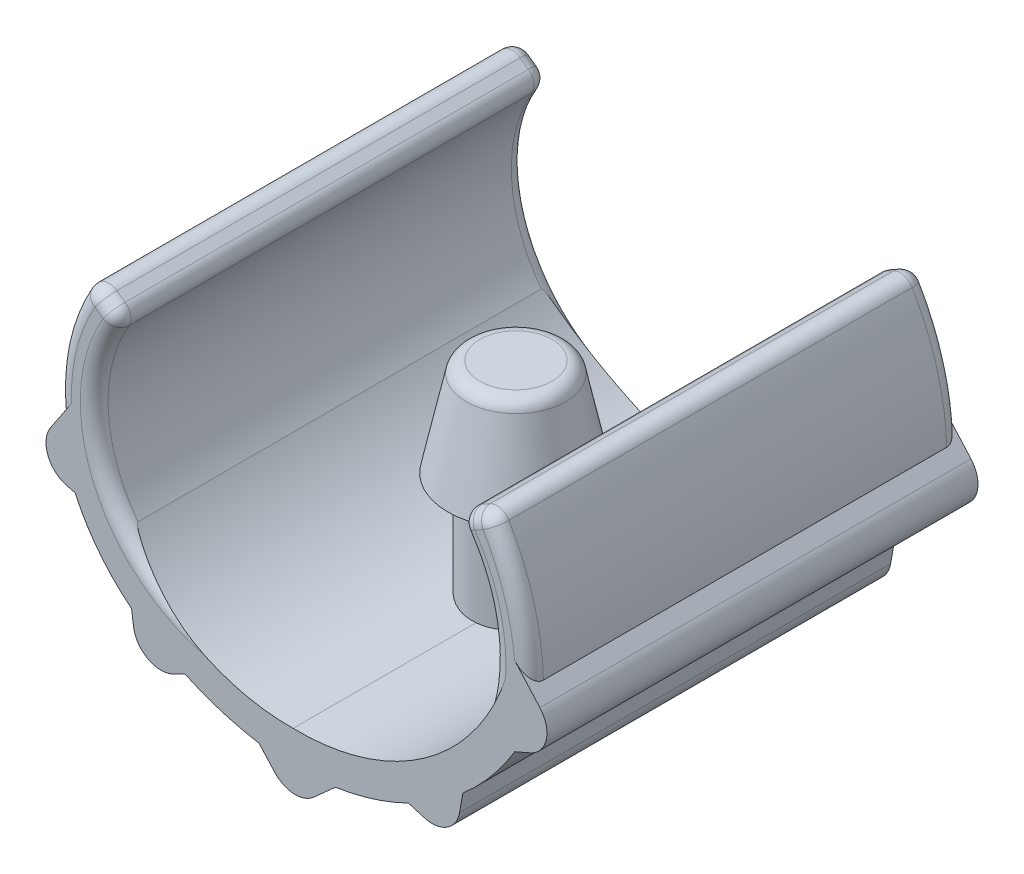
SolidWorks part; units mm, degrees
ref_plane "Front Plane" through (0, 0, 0) normal (0, 0, 1) x (1, 0, 0)
ref_plane "Top Plane" through (0, 0, 0) normal (0, 1, 0) x (1, 0, 0)
ref_plane "Right Plane" through (0, 0, 0) normal (1, 0, 0) x (0, 0, -1)
sketch "Sketch1" plane through (0, 0, 0) normal (0, 0, 1) x (1, 0, 0)
  line L0 (-248.758, 1.0447) -> (261.9086, 1.0447) construction
  line L1 (-173.9494, 133.0489) -> (-205.5576, 155.7204)
  line L2 (163.6266, 136.7807) -> (197.8189, 155.7204)
  line L3 (-237.9986, 19.6907) -> (-268.7856, -26.37)
  line L4 (-268.7856, -26.37) -> (-221.5833, -38.0173)
  line L5 (-164.251, -111.1614) -> (-156.9102, -164.9208)
  line L6 (-156.9102, -164.9208) -> (-109.8369, -141.7643)
  line L7 (-34.694, -164.9208) -> (0, -203.3288)
  line L8 (0, -203.3288) -> (42.8865, -164.9208)
  line L9 (172.3349, -105.3153) -> (163.6266, -155.5211)
  line L10 (163.6266, -155.5211) -> (117.0575, -141.7643)
  line L11 (240.1322, 20.9284) -> (276.7092, -20.0955)
  line L12 (276.7092, -20.0955) -> (225.1621, -42.4505)
  line L13 (0, -352) -> (0, 352) construction
  arc A0 (-173.9494, 133.0489) -> (-171.8112, -45.6554) centre (-51.4028, 45.1503) ccw
  arc A1 (-171.8112, -45.6554) -> (0, -134.4778) centre (-3.7953, 68.7613) ccw
  arc A2 (0, -134.4778) -> (188.7489, -37.6724) centre (5.7404, 86.7417) ccw
  arc A3 (188.7489, -37.6724) -> (163.6266, 136.7807) centre (31.1848, 28.6729) ccw
  arc A4 (-205.5576, 155.7204) -> (-237.9986, 19.6907) centre (-40.897, 44.5682) ccw
  arc A5 (-109.8369, -141.7643) -> (-34.694, -164.9208) centre (12.2742, 120.9887) ccw
  arc A6 (42.8865, -164.9208) -> (117.0575, -141.7643) centre (4.0963, 89.6894) ccw
  arc A7 (240.1322, 20.9284) -> (197.8189, 155.7204) centre (-14.6281, 14.9926) ccw
  arc A8 (172.3349, -105.3153) -> (225.1621, -42.4505) centre (4.0963, 89.6894) ccw
  arc A9 (-221.5833, -38.0173) -> (-164.251, -111.1614) centre (-40.897, 44.5682) ccw
  point P22 (-164.4772, 144.5832)
  point P30 (-170.9582, -47.47)
  point P34 (0, -134.4778)
  point P37 (188.7489, -37.6724)
  point P38 (167.4902, 149.616)
  point P39 (163.6266, 142.761)
  point P40 (188.7489, 166.9728)
  point P41 (-161.5749, -112.8309)
  point P42 (-164.251, -111.1614)
  point P43 (0, 0)
  point P44 (195.2203, 163.4228)
  point P45 (163.6266, 132.7512)
  point P46 (197.8189, 155.7204)
  point P47 (-173.9494, -38.0173)
  point P48 (-205.5576, 155.7204)
  dimension "D1" = 337.5761
extrude "Boss-Extrude2" add sketch "Sketch1" along normal blind 438
scale "Scale2" bodies to scale 103 scale about centroid uniform scaling yes scale factor 0.0354
fillet "Fillet1" radius 1 5 edges at (9.0204, -43.6728, 219) (5.0173, -48.4669, 219) (-0.7751, -50.1593, 219) (-6.3297, -48.7996, 219) (-10.2901, -43.8949, 219)
fillet "Fillet3" radius 0.5 4 edges at (-6.9329, -38.2515, 219) (-8.0518, -37.4489, 219) (5.0173, -38.1194, 219) (6.2277, -37.4489, 219)
ref_plane "Plane1" through (0, 0, 226.7526) normal (0, 0, 1) x (1, 0, 0)
ref_plane "Plane2" through (0, 0, 218.5826) normal (0, 0, 1) x (1, 0, 0)
sketch "Sketch2" plane through (0, 0, 218.5826) normal (0, 0, 1) x (1, 0, 0)
  line L0 (-7.1238, -38.2766) -> (5.2591, -38.2766) construction
  line L1 (-0.9323, -38.2766) -> (-0.9323, -47.7163) construction
  line L2 (-0.9323, -47.7163) -> (-6.7505, -47.1956)
  line L3 (-9.9505, -47.1956) -> (-0.9323, -47.7163)
  arc A0 (-7.1834, -38.6344) -> (-7.3218, -37.9726) centre (-7.6132, -38.3789) ccw construction
  arc A1 (5.5168, -37.8427) -> (5.3447, -38.5599) centre (5.7591, -38.2801) ccw construction
  arc A2 (-0.7751, -47.722) -> (5.9066, -44.295) centre (-0.5719, -39.8908) ccw construction
ref_plane "Plane3" through (0, -47.722, 0) normal (0, -1, 0) x (-1, 0, 0)
sketch "Sketch4" plane through (0, -47.722, 0) normal (0, -1, 0) x (-1, 0, 0)
  line L0 (8.3442, -220.6084) -> (8.3442, -217.4084)
  arc A0 (8.3442, -220.6084) -> (8.3442, -217.4084) centre (8.3442, -219.0084) ccw
  dimension "D1" = 1.6
ref_plane "Plane4" through (0, -43.922, 0) normal (0, -1, 0) x (-1, 0, 0)
sketch "Sketch5" plane through (0, -43.922, 0) normal (0, -1, 0) x (-1, 0, 0)
  line L0 (2.483, -218.9766) -> (2.483, -218.1886)
  arc A1 (2.483, -218.9766) -> (2.483, -218.1886) centre (0.9323, -218.5826) cw
  dimension "D1" = 1.6
extrude "Boss-Extrude4" add sketch "Sketch5" along direction (0, -1, 0) on the side of the normal up to surface (3.5659 mm away) up to face at (2.7845, -46.4349, 219)
sketch "Sketch8" plane through (0, -43.922, 0) normal (0, -1, 0) x (-1, 0, 0)
  line L0 (0.9323, -216.9826) -> (0.9323, -220.1826)
  arc A0 (0.9323, -220.1826) -> (0.9323, -216.9826) centre (0.9323, -218.5826) ccw
  arc A1 (2.483, -218.1886) -> (2.483, -218.9766) centre (0.9323, -218.5826) ccw construction
  dimension "D1" = 1.6
  dimension "D2" = 3.2
extrude "Boss-Extrude5" add sketch "Sketch8" along direction (0, -1, 0) on the side of the normal up to surface (3.8012 mm away) up to face at (-2.9351, -46.9304, 218.8609)
sketch "Sketch9" plane through (0, -43.922, 0) normal (0, 1, 0) x (1, 0, 0)
  circle A0 centre (-0.9323, -218.5826) radius 2.45
  point P2 (0, 0)
  dimension "D1" = 4.9
extrude "Boss-Extrude6" add sketch "Sketch9" along normal blind 3.5 draft 12
fillet "Fillet4" radius 0.5 1 edges at (-0.9323, -40.422, 220.2887)
fillet "Fillet5" radius 0.5 20 edges at (7.3839, -39.9627, 226.7526) (6.1869, -37.6339, 226.7526) (6.3521, -41.3563, 226.7526) (5.2729, -38.1634, 226.7526) (7.3839, -39.9627, 211.2474) (6.1869, -37.6339, 211.2474) (6.3521, -41.3563, 211.2474) (5.2729, -38.1634, 211.2474) (-7.9254, -41.6557, 211.2474) (-7.1238, -38.2766, 211.2474) (-9.1228, -40.0234, 211.2474) (-8.0163, -37.6786, 211.2474) (-7.9254, -41.6557, 226.7526) (-7.1238, -38.2766, 226.7526) (-9.1228, -40.0234, 226.7526) (-8.0163, -37.6786, 226.7526) (5.6648, -37.7608, 226.7526) (5.6648, -37.7608, 211.2474) (-7.4695, -37.8666, 211.2474) (-7.4695, -37.8666, 226.7526)
